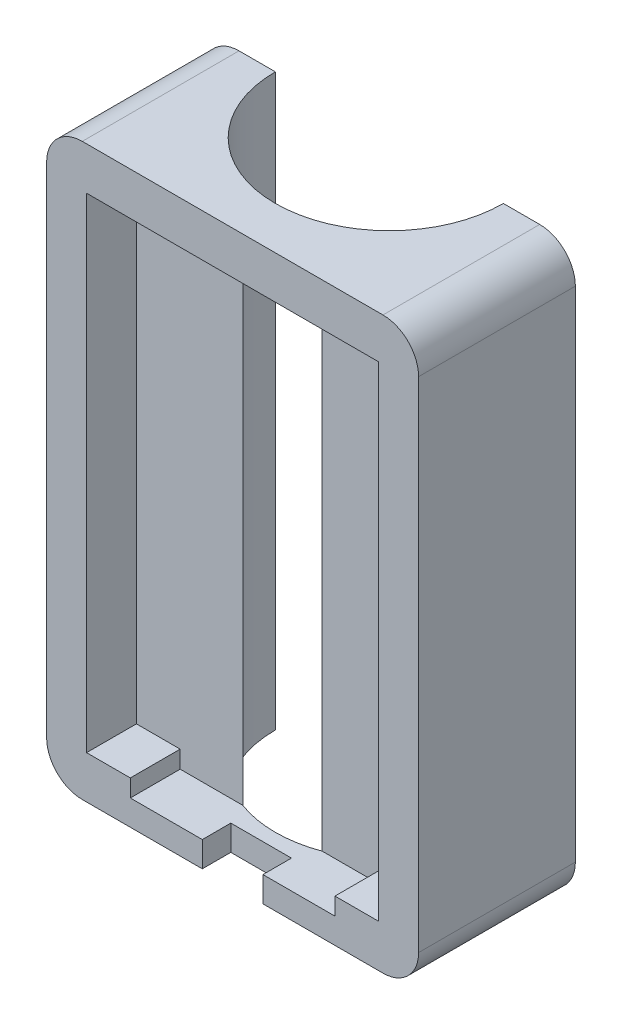
SolidWorks part; units mm, degrees
ref_plane "Plan de face" through (0, 0, 0) normal (0, 0, 1) x (1, 0, 0)
ref_plane "Plan de dessus" through (0, 0, 0) normal (0, 1, 0) x (1, 0, 0)
ref_plane "Plan de droite" through (0, 0, 0) normal (1, 0, 0) x (0, 0, -1)
sketch "Esquisse1" plane through (0, 0, 0) normal (0, 0, 1) x (1, 0, 0)
  line L1 (-41.2248, -2.0065) -> (10.9752, -2.0065)
  line L2 (-41.2248, -2.0065) -> (-41.2248, -82.0065)
  line L3 (-41.2248, -82.0065) -> (10.9752, -82.0065)
  line L4 (10.9752, -2.0065) -> (10.9752, -82.0065)
extrude "Boss.-Extru.2" add sketch "Esquisse1" along normal blind 22
sketch "Esquisse2" plane through (0, -82.0065, 0) normal (0, -1, 0) x (1, 0, 0)
  line L0 (-41.2248, 0) -> (10.9752, 0) construction
  circle A0 centre (-15.1248, 0) radius 16
sketch "Esquisse3" plane through (0, 0, 22) normal (0, 0, 1) x (1, 0, 0)
  line L0 (-41.2248, -2.0065) -> (-41.2248, -82.0065) construction
  line L1 (-39.4848, -5.5677) -> (9.2352, -5.5677)
  line L2 (-39.4848, -5.5677) -> (-39.4848, -78.4453)
  line L3 (-39.4848, -78.4453) -> (9.2352, -78.4453)
  line L4 (9.2352, -5.5677) -> (9.2352, -78.4453)
  line L5 (10.9752, -82.0065) -> (10.9752, -2.0065) construction
  line L6 (10.9752, -2.0065) -> (-41.2248, -2.0065) construction
  line L7 (-31.1248, -82.0065) -> (0.8752, -82.0065) construction
  dimension "D1" = 1.74
  dimension "D2" = 1.74
  dimension "D3" = 3.5612
  dimension "D4" = 3.5612
extrude "Enlèv. mat.-Extru.1" cut sketch "Esquisse3" against normal blind 5
fillet "Congé1" radius 10 4 edges at (-39.4848, -78.4453, 19.5) (9.2352, -78.4453, 19.5) (9.2352, -5.5677, 19.5) (-39.4848, -5.5677, 19.5)
fillet "Congé2" radius 5 4 edges at (-41.2248, -82.0065, 11) (10.9752, -82.0065, 11) (10.9752, -2.0065, 11) (-41.2248, -2.0065, 11)
sketch "Esquisse5" plane through (0, 0, 17) normal (0, 0, 1) x (1, 0, 0)
  line L0 (-35.6248, -42.0065) -> (5.3752, -42.0065) construction
  line L1 (-35.6248, -8.0065) -> (5.3752, -8.0065)
  line L2 (-35.6248, -8.0065) -> (-35.6248, -15.5677)
  line L3 (-35.6248, -76.0065) -> (-29.4848, -76.0065)
  line L4 (5.3752, -8.0065) -> (5.3752, -15.5677)
  line L5 (5.9752, -2.0065) -> (-36.2248, -2.0065) construction
  line L6 (5.3752, -68.4453) -> (5.3752, -76.0065)
  line L7 (-0.7648, -76.0065) -> (5.3752, -76.0065)
  line L8 (-29.4848, -8.0065) -> (-0.7648, -8.0065)
  line L9 (10.9752, -77.0065) -> (10.9752, -7.0065) construction
  line L10 (-35.6248, -68.4453) -> (-35.6248, -15.5677)
  line L11 (5.3752, -15.5677) -> (5.3752, -68.4453)
  line L13 (-35.6248, -15.5677) -> (-35.6248, -8.0065)
  line L15 (-29.4848, -8.0065) -> (-35.6248, -8.0065)
  line L16 (-39.4848, -15.5677) -> (-39.4848, -5.5677)
  line L17 (-39.4848, -5.5677) -> (-29.4848, -5.5677)
  line L18 (-15.1248, -8.0065) -> (-15.1248, -76.0065) construction
  line L26 (9.2352, -15.5677) -> (9.2352, -5.5677)
  line L27 (9.2352, -5.5677) -> (-0.7648, -5.5677)
  line L29 (9.2352, -68.4453) -> (9.2352, -78.4453)
  line L30 (9.2352, -78.4453) -> (-0.7648, -78.4453)
  line L31 (-0.7648, -78.4453) -> (-0.7648, -76.0065)
  line L33 (-29.4848, -78.4453) -> (-29.4848, -76.0065)
  line L34 (-39.4848, -78.4453) -> (-29.4848, -78.4453)
  line L35 (-39.4848, -68.4453) -> (-39.4848, -78.4453)
  line L36 (-35.6248, -68.4453) -> (-35.6248, -76.0065)
  line M5 (-39.4848, -15.5677) -> (-39.4848, -68.4453)
  arc M6 (-39.4848, -68.4453) -> (-29.4848, -78.4453) centre (-29.4848, -68.4453) ccw
  arc M8 (-0.7648, -78.4453) -> (9.2352, -68.4453) centre (-0.7648, -68.4453) ccw
  line M9 (9.2352, -68.4453) -> (9.2352, -15.5677)
  arc M10 (9.2352, -15.5677) -> (-0.7648, -5.5677) centre (-0.7648, -15.5677) ccw
  line M11 (-0.7648, -5.5677) -> (-29.4848, -5.5677)
  arc M12 (-29.4848, -5.5677) -> (-39.4848, -15.5677) centre (-29.4848, -15.5677) ccw
  dimension "D1" = 41
  dimension "D2" = 68
  dimension "D3" = 6
  dimension "D4" = 5.6
extrude "Boss.-Extru.4" add sketch "Esquisse5" along normal blind 5 contours L36 L10 L2 L1 L4 L11 L6 L7 L31 L33 L3 M8 M9 M10 M11 M12 M5 M6 region at (-36.5014, -11.7871, 17)
extrude "Enlèv. mat.-Extru.3" cut sketch "Esquisse2" against normal through all contours A0
sketch "Esquisse7" plane through (0, 0, 17) normal (0, 0, 1) x (1, 0, 0)
  line L0 (-35.6248, -8.0065) -> (5.3752, -8.0065)
  line L1 (5.3752, -8.0065) -> (5.3752, -76.0065)
  line L2 (5.3752, -76.0065) -> (-0.7648, -76.0065)
  line L3 (-0.7648, -76.0065) -> (-0.7648, -78.4453)
  line L4 (-0.7648, -78.4453) -> (-29.4848, -78.4453)
  line L5 (-29.4848, -78.4453) -> (-29.4848, -76.0065)
  line L6 (-29.4848, -76.0065) -> (-35.6248, -76.0065)
  line L7 (-35.6248, -76.0065) -> (-35.6248, -8.0065)
extrude "Enlèv. mat.-Extru.5" cut sketch "Esquisse7" against normal blind 2
sketch "Esquisse8" plane through (0, 0, 22) normal (0, 0, 1) x (1, 0, 0)
  line L1 (-19.3798, -78.4453) -> (-10.8698, -78.4453)
  line L2 (-19.3798, -78.4453) -> (-19.3798, -82.0065)
  line L3 (-19.3798, -82.0065) -> (-10.8698, -82.0065)
  line L4 (-10.8698, -78.4453) -> (-10.8698, -82.0065)
  line L7 (-0.7648, -78.4453) -> (-0.7648, -76.0065) construction
  line L8 (-29.4848, -76.0065) -> (-29.4848, -78.4453) construction
  dimension "D1" = 10.105
  dimension "D2" = 10.105
extrude "Enlèv. mat.-Extru.6" cut sketch "Esquisse8" against normal blind 4
